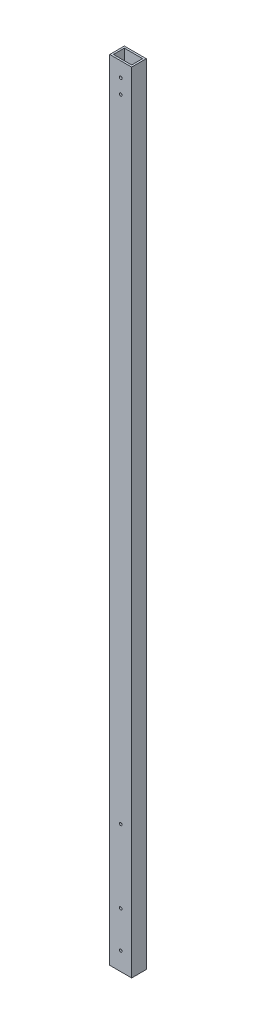
SolidWorks part; units mm, degrees
material "6061-T6 (SS)"
ref_plane "Front Plane" through (0, 0, 0) normal (0, 0, 1) x (1, 0, 0)
ref_plane "Top Plane" through (0, 0, 0) normal (0, 1, 0) x (1, 0, 0)
ref_plane "Right Plane" through (0, 0, 0) normal (1, 0, 0) x (0, 0, -1)
sketch "Sketch2" plane through (0, 0, 0) normal (0, 1, 0) x (1, 0, 0)
  line L1 (-19.05, -12.7) -> (19.05, -12.7)
  line L2 (-19.05, -12.7) -> (-19.05, 12.7)
  line L3 (-19.05, 12.7) -> (19.05, 12.7)
  line L4 (19.05, -12.7) -> (19.05, 12.7)
  line L5 (-19.05, -12.7) -> (19.05, 12.7) construction
  line L6 (-19.05, 12.7) -> (19.05, -12.7) construction
  line L7 (15.875, -9.525) -> (-15.875, -9.525)
  line L8 (15.875, -9.525) -> (15.875, 9.525)
  line L9 (15.875, 9.525) -> (-15.875, 9.525)
  line L10 (-15.875, -9.525) -> (-15.875, 9.525)
  line L11 (15.875, -9.525) -> (-15.875, 9.525) construction
  line L12 (15.875, 9.525) -> (-15.875, -9.525) construction
  point P0 (0, 0)
  point P6 (0, 0)
  dimension "D1" = 38.1
  dimension "D2" = 25.4
  dimension "D3" = 3.175
  dimension "D4" = 3.175
extrude "Boss-Extrude1" add sketch "Sketch2" along normal blind 1371.6
sketch "Sketch3" plane through (0, 0, 12.7) normal (0, 0, 1) x (1, 0, 0)
  line L0 (19.05, 0) -> (19.05, 31.75) construction
  line L1 (19.05, 1371.6) -> (19.05, 0) construction
  line L2 (19.05, 31.75) -> (0, 31.75) construction
  line L3 (0, 31.75) -> (0, 222.25) construction
  circle A0 centre (0, 31.75) radius 2.413
  circle A1 centre (0, 222.25) radius 2.413
  circle A2 centre (0, 95.25) radius 2.413
  dimension "D3" = 4.826
  dimension "D5" = 4.826
  dimension "D6" = 63.5
  dimension "D1" = 19.05
  dimension "D2" = 31.75
  dimension "D4" = 190.5
extrude "Cut-Extrude1" cut sketch "Sketch3" against normal up to surface (25.4 mm away) up to face at (0, 685.8, -12.7)
sketch "Sketch4" plane through (0, 0, 12.7) normal (0, 0, 1) x (1, 0, 0)
  line L0 (0, 1371.6) -> (0, 1262.4123) construction
  line L1 (-19.05, 1371.6) -> (19.05, 1371.6) construction
  circle A0 centre (0, 1346.2) radius 2.413
  circle A1 centre (0, 1320.8) radius 2.413
  dimension "D1" = 4.826
  dimension "D2" = 25.4
  dimension "D3" = 25.4
extrude "Cut-Extrude2" cut sketch "Sketch4" against normal up to surface (25.4 mm away) up to face at (2.413, 31.75, -12.7)
